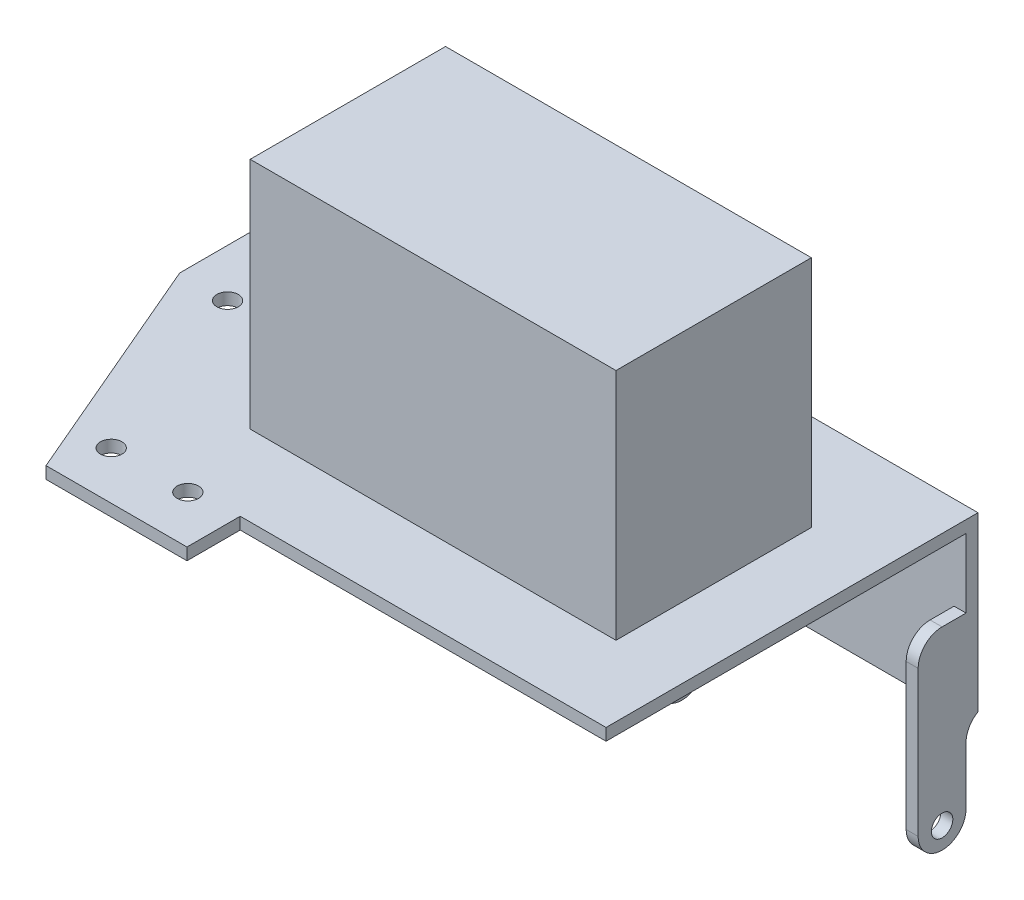
SolidWorks part; units mm, degrees
ref_plane "Front Plane" through (0, 0, 0) normal (0, 0, 1) x (1, 0, 0)
ref_plane "Top Plane" through (0, 0, 0) normal (0, 1, 0) x (1, 0, 0)
ref_plane "Right Plane" through (0, 0, 0) normal (1, 0, 0) x (0, 0, -1)
sketch "Sketch1" plane through (0, 0, 0) normal (0, 1, 0) x (1, 0, 0)
  line L0 (0, 0) -> (0, -25.4)
  line L1 (0, -25.4) -> (13.2588, -56.388)
  line L2 (13.2588, -56.388) -> (31.9532, -56.388)
  line L3 (31.9532, -56.388) -> (31.9532, -49.3268)
  line L4 (31.9532, -49.3268) -> (80.4672, -49.3268)
  line L5 (80.4672, -49.3268) -> (80.4672, 0)
  line L6 (80.4672, 0) -> (0, 0)
  dimension "D1" = 80.4672
  dimension "D2" = 49.3268
  dimension "D3" = 56.388
  dimension "D4" = 25.4
  dimension "D5" = 48.514
  dimension "D6" = 18.6944
extrude "Boss-Extrude1" add sketch "Sketch1" along normal blind 1.5875
sketch "Sketch2" plane through (0, 0, 0) normal (0, -1, 0) x (1, 0, 0)
  line L1 (80.4672, 0) -> (44.3992, 0)
  line L2 (80.4672, 0) -> (80.4672, 1.5875)
  line L3 (80.4672, 1.5875) -> (44.3992, 1.5875)
  line L4 (44.3992, 0) -> (44.3992, 1.5875)
  dimension "D1" = 1.5875
  dimension "D2" = 36.068
extrude "Boss-Extrude2" add sketch "Sketch2" along normal blind 21.2725
sketch "Sketch3" plane through (0, 0, 1.5875) normal (0, 0, 1) x (1, 0, 0)
  line L0 (80.4672, -21.2725) -> (80.4672, 0) construction
  line L1 (80.4672, -9.144) -> (78.8797, -9.144)
  line L2 (80.4672, -9.144) -> (80.4672, -34.798)
  line L3 (80.4672, -34.798) -> (78.8797, -34.798)
  line L4 (78.8797, -9.144) -> (78.8797, -34.798)
  line L5 (80.4672, 0) -> (44.3992, 0) construction
  line L7 (62.4332, 0) -> (62.4332, -21.2725) construction
  line L9 (80.4672, -21.2725) -> (44.3992, -21.2725) construction
  line L10 (45.9867, -9.144) -> (45.9867, -34.798)
  line L11 (44.3992, -34.798) -> (45.9867, -34.798)
  line L12 (44.3992, -9.144) -> (44.3992, -34.798)
  line L13 (44.3992, -9.144) -> (45.9867, -9.144)
  dimension "D1" = 1.5875
  dimension "D2" = 9.144
  dimension "D3" = 34.798
extrude "Boss-Extrude3" add sketch "Sketch3" along normal blind 6.35
fillet "Fillet1" radius 3.175 8 edges at (79.6735, -21.2725, 1.5875) (45.193, -21.2725, 1.5875) (45.193, -9.144, 7.9375) (45.193, -34.798, 7.9375) (45.193, -34.798, 1.5875) (79.6735, -9.144, 7.9375) (79.6735, -34.798, 1.5875) (79.6735, -34.798, 7.9375)
hole_wizard "Hole1" positions "Sketch6" profile "Sketch5" legacy
sketch "Sketch6" plane through (0, 0, 0) normal (0, 0, -1) x (-1, 0, 0)
  line L0 (-62.4332, -21.2725) -> (-62.4332, 1.5875) construction
  line L1 (-45.9867, -21.2725) -> (-78.8797, -21.2725) construction
  line L2 (-80.4672, 1.5875) -> (0, 1.5875) construction
  line L12 (-44.3992, -10.6363) -> (-80.4672, -10.6363) construction
  line L13 (-44.3992, -21.2725) -> (-44.3992, 0) construction
  line L14 (-80.4672, 1.5875) -> (-80.4672, -21.2725) construction
  point P0 (-62.4332, -10.6363)
sketch "Sketch5" plane through (62.4332, -10.6363, 0) normal (1, 0, 0) x (0, 1, 0)
  line L0 (0, 0) -> (0, 15.875)
  line L1 (0, 15.875) -> (2.54, 15.875)
  line L2 (2.54, 15.875) -> (2.54, 0)
  line L3 (2.54, 0) -> (0, 0)
  line L4 (0, 110) -> (0, -10) construction
  dimension "Diameter" = 5.08
  dimension "Depth" = 15.875
hole_wizard "Hole2" positions "Sketch8" profile "Sketch7" legacy end condition through all
sketch "Sketch8" plane through (80.4672, 0, 0) normal (1, 0, 0) x (0, 0, -1)
  line L0 (-1.5875, -31.623) -> (-1.5875, -24.0221) construction
  point P0 (-4.7625, -31.9532)
  dimension "D1" = 3.175
  dimension "D2" = 2.8448
sketch "Sketch7" plane through (80.4672, -31.9532, 4.7625) normal (0, 1, 0) x (0, 0, -1)
  line L0 (0, 0) -> (0, 80.4672)
  line L1 (0, 80.4672) -> (1.4224, 80.4672)
  line L2 (1.4224, 80.4672) -> (1.4224, 0)
  line L3 (1.4224, 0) -> (0, 0)
  line L4 (0, 110) -> (0, -10) construction
  dimension "Diameter" = 2.8448
  dimension "Depth" = 80.4672
sketch "Sketch9" plane through (0, 1.5875, 0) normal (0, 1, 0) x (1, 0, 0)
  line L0 (0, 0) -> (0, -25.4) construction
  line L1 (71.12, -12.7508) -> (22.606, -12.7508)
  line L2 (71.12, -12.7508) -> (71.12, -38.6588)
  line L3 (71.12, -38.6588) -> (22.606, -38.6588)
  line L4 (22.606, -12.7508) -> (22.606, -38.6588)
  line L5 (31.9532, -49.3268) -> (80.4672, -49.3268) construction
  dimension "D1" = 48.514
  dimension "D2" = 25.908
  dimension "D3" = 22.606
  dimension "D4" = 10.668
extrude "Boss-Extrude4" add sketch "Sketch9" along normal blind 30.988
hole_wizard "Hole3" positions "Sketch11" profile "Sketch10" legacy end condition through all
sketch "Sketch11" plane through (0, 1.5875, 0) normal (0, 1, 0) x (-1, 0, 0)
  line L1 (-22.606, 56.388) -> (-22.606, 43.688) construction
  line L2 (-13.2588, 56.388) -> (-31.9532, 56.388) construction
  point P0 (-25.7175, 50.038)
  dimension "D1" = 12.7
  dimension "D2" = 3.1115
  dimension "D3" = 6.35
sketch "Sketch10" plane through (25.7175, 1.5875, 50.038) normal (1, 0, 0) x (0, 0, 1)
  line L0 (0, 0) -> (0, 36.3855)
  line L1 (0, 36.3855) -> (1.4224, 36.3855)
  line L2 (1.4224, 36.3855) -> (1.4224, 0)
  line L3 (1.4224, 0) -> (0, 0)
  line L4 (0, 110) -> (0, -10) construction
  dimension "Diameter" = 2.8448
  dimension "Depth" = 36.3855
pattern_linear "LPattern1" count 2 spacing 10.16 along (-1, 0, 0) of "Hole3"
hole_wizard "Hole4" positions "Sketch13" profile "Sketch12" legacy end condition through all
sketch "Sketch13" plane through (0, 1.5875, 0) normal (0, 1, 0) x (-1, 0, 0)
  line L0 (0, 0) -> (0, 25.4) construction
  line L1 (-80.4672, 0) -> (0, 0) construction
  point P0 (-6.35, 25.4)
  dimension "D1" = 6.35
  dimension "D2" = 25.4
sketch "Sketch12" plane through (6.35, 1.5875, 25.4) normal (1, 0, 0) x (0, 0, 1)
  line L0 (0, 0) -> (0, 36.3855)
  line L1 (0, 36.3855) -> (1.4224, 36.3855)
  line L2 (1.4224, 36.3855) -> (1.4224, 0)
  line L3 (1.4224, 0) -> (0, 0)
  line L4 (0, 110) -> (0, -10) construction
  dimension "Diameter" = 2.8448
  dimension "Depth" = 36.3855
pattern_linear "LPattern2" count 2 spacing 28.575 along (1, 0, 0) of "Hole4"
ref_point "Point1"
ref_point "Point2"
ref_point "Point3"
ref_point "Point4"
ref_point "Point5"
